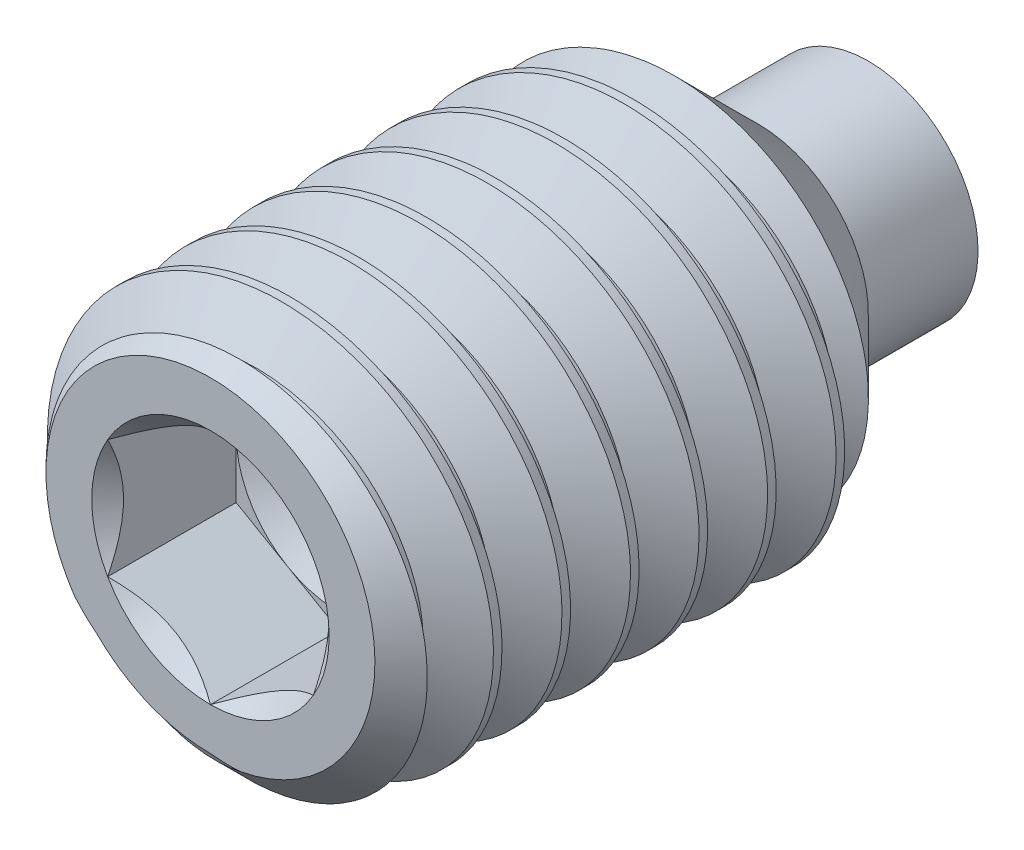
SolidWorks part; units mm, degrees
ref_plane "Front" through (0, 0, 0) normal (0, 0, 1) x (1, 0, 0)
ref_plane "Top" through (0, 0, 0) normal (0, 1, 0) x (1, 0, 0)
ref_plane "Right" through (0, 0, 0) normal (1, 0, 0) x (0, 0, -1)
sketch "Sketch22" plane through (0, 0, 0) normal (1, 0, 0) x (0, 0, -1)
  line L0 (-4.8, 0) -> (-4.8, 2.4)
  line L1 (-4.8, 2.4) -> (-4.2, 3)
  line L2 (-4.2, 3) -> (1.8, 3)
  line L3 (1.8, 3) -> (3.2, 1.6)
  line L5 (4.8, 0) -> (-4.8, 0)
  line L6 (4.8, 0) -> (3.2, 0) construction
  line L7 (3.2, 0) -> (3.2, 1.6) construction
  line L9 (-4.2, -3) -> (1.8, -3) construction
  line L10 (3.2, 1.6) -> (4.8, 1.6)
  line L11 (4.8, 1.6) -> (4.8, 0)
  line L12 (4.8, 1.6) -> (4.8, -1.6) construction
  dimension "Screw Dia" = 6
  dimension "D3" = 45
  dimension "D6" = 45
  dimension "D7" = 4.8
  dimension "A" = 3.2
  dimension "B" = 1.6
  dimension "Length" = 8
revolve "Revolve1" add sketch "Sketch22" angle 360 about L6
ref_plane "Plane2" through (0, 0, -3.2) normal (0, 0, 1) x (1, 0, 0)
sketch "Sketch27" plane through (0, 0, -3.2) normal (0, 0, 1) x (1, 0, 0)
  circle A0 centre (0, 0) radius 3
curve "Helix/Spiral1" pitch 1 height 9 radius 3 centre (0, 0, -3.2) axis (0, 0, 1) start towards (0, 1, 0)
sketch "Sketch6" plane through (0, 0, 0) normal (1, 0, 0) x (0, 0, -1)
  line L0 (3.3875, 2.6752) -> (3.8875, 2.6752) construction
  line L3 (-4.2, 3) -> (1.8, 3) construction
  line L4 (3.7, 2.3505) -> (3.575, 2.3505)
  line L5 (3.575, 2.3505) -> (3.2, 3)
  line L6 (3.7, 2.3505) -> (4.075, 3)
  line L7 (4.075, 3) -> (3.2, 3)
  dimension "D2" = 0.125
  dimension "D3" = 60
  dimension "D1" = 0.5
sweep "Cut-Sweep1" cut profiles "Sketch6" path "Helix/Spiral1"
sketch "Sketch30" plane through (0, 0, 4.8) normal (0, 0, 1) x (1, 0, 0)
  line L1 (1.5, -0.866) -> (1.5, 0.866)
  line L2 (1.5, 0.866) -> (0, 1.7321)
  line L3 (0, 1.7321) -> (-1.5, 0.866)
  line L4 (-1.5, 0.866) -> (-1.5, -0.866)
  line L5 (-1.5, -0.866) -> (0, -1.7321)
  line L6 (0, -1.7321) -> (1.5, -0.866)
  circle A0 centre (0, 0) radius 1.5 construction
  dimension "hex" = 3
extrude "Cut-Extrude1" cut sketch "Sketch30" against normal blind 1.875
sketch "Sketch31" plane through (0, 0, 4.8) normal (0, 0, 1) x (1, 0, 0)
  circle A0 centre (0, 0) radius 1.7321
extrude "Cut-Extrude2" cut sketch "Sketch31" against normal through all draft 45
sketch "Sketch32" plane through (0, 0, 2.925) normal (0, 0, 1) x (1, 0, 0)
  circle A0 centre (0, 0) radius 1.5 construction
  circle A1 centre (0, 0) radius 1.5
extrude "Cut-Extrude3" cut sketch "Sketch32" against normal through all draft 60
sketch "Sketch29" plane through (0, 0, 0) normal (1, 0, 0) x (0, 0, -1)
  line L2 (-4.2, -3) -> (1.8, -3) construction
  point P1 (-4.8, 3)
  point P2 (3.2, 1.6)
  point P3 (4.8, 1.6)
  point P4 (4.8, -1.6)
  point P5 (4.8, -3)
  point P6 (-1.2, -3)
  point P7 (4.8, 3)
  dimension "D1" = 3
sketch "Sketch33" plane through (0, 0, 4.8) normal (0, 0, 1) x (1, 0, 0)
  circle A0 centre (0, 0) radius 3
equation "\"D7@Sketch22\"=\"Screw Dia@Sketch22\"*.8"
equation "\"D3@Helix/Spiral1\" = \"Length@Sketch22\" + \"D4@Helix/Spiral1\""
equation "\"D2@Sketch6\" = \"D4@Helix/Spiral1\" * .125"
equation "\"D1@Sketch6\" = \"D4@Helix/Spiral1\" * .5"
equation "\"D1@Sketch29\" = \"D4@Helix/Spiral1\" * 3"
equation "\"D1@Cut-Extrude1\" = \"hex@Sketch30\" * .625"
